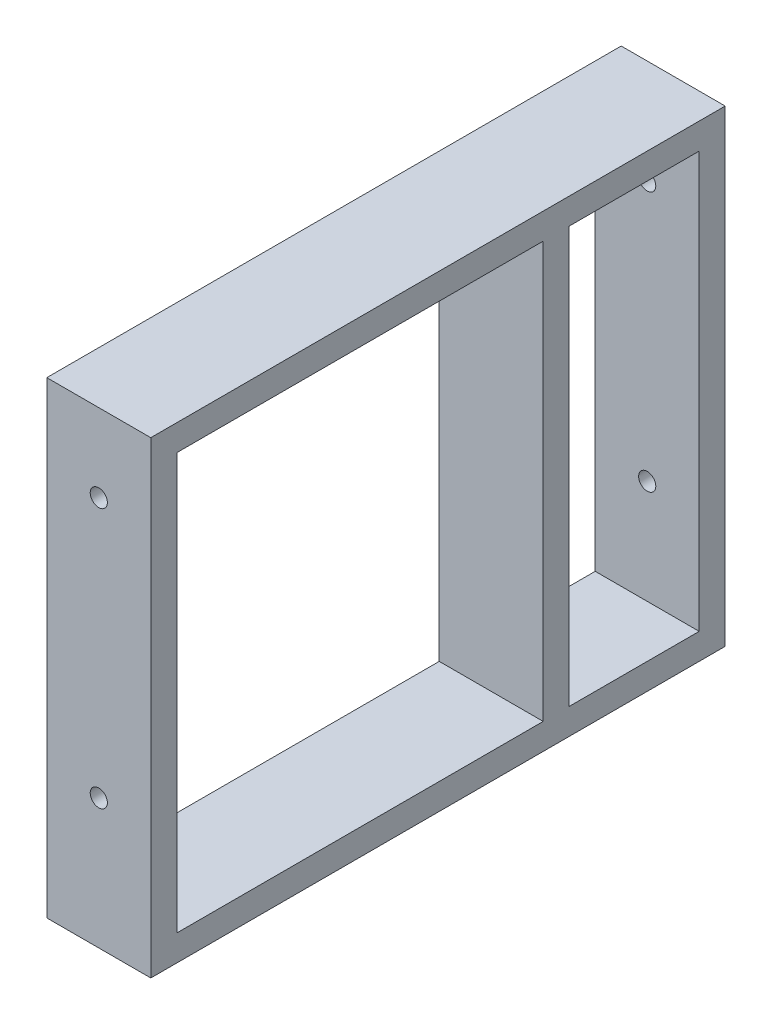
SolidWorks part; units mm, degrees
ref_plane "Front Plane" through (0, 0, 0) normal (0, 0, 1) x (1, 0, 0)
ref_plane "Top Plane" through (0, 0, 0) normal (0, 1, 0) x (1, 0, 0)
ref_plane "Right Plane" through (0, 0, 0) normal (1, 0, 0) x (0, 0, -1)
sketch "Sketch1" plane through (0, 0, 0) normal (1, 0, 0) x (0, 0, -1)
  line L1 (-55.2375, -45) -> (55.2375, -45)
  line L2 (-55.2375, -45) -> (-55.2375, 45)
  line L3 (-55.2375, 45) -> (55.2375, 45)
  line L4 (55.2375, -45) -> (55.2375, 45)
  line L5 (-55.2375, -45) -> (55.2375, 45) construction
  line L6 (-55.2375, 45) -> (55.2375, -45) construction
  line L7 (-50.2375, -40) -> (50.2375, -40)
  line L8 (-50.2375, -40) -> (-50.2375, 40)
  line L9 (-50.2375, 40) -> (50.2375, 40)
  line L10 (50.2375, -40) -> (50.2375, 40)
  line L11 (-50.2375, -40) -> (50.2375, 40) construction
  line L12 (-50.2375, 40) -> (50.2375, -40) construction
  line L13 (20.2375, -40) -> (25.2375, -40)
  line L14 (20.2375, -40) -> (20.2375, 40)
  line L15 (20.2375, 40) -> (25.2375, 40)
  line L16 (25.2375, -40) -> (25.2375, 40)
  line L17 (20.2375, -40) -> (25.2375, 40) construction
  line L18 (20.2375, 40) -> (25.2375, -40) construction
  point P0 (0, 0)
  point P6 (0, 0)
  point P11 (22.7375, 0)
  point P16 (0, 0)
  dimension "D1" = 110.475
  dimension "D2" = 90
  dimension "D3" = 5
  dimension "D4" = 5
  dimension "D5" = 5
  dimension "D6" = 25
extrude "Boss-Extrude1" add sketch "Sketch1" along normal blind 20 contours L1 L4 L3 L2 L10 L7 L8 L9 | L7 L16 L9 L14 region at (0, 0, 53.8126) region at (0, 0, -22.7375)
hole_wizard "M4 Clearance Hole1" positions "Sketch2" profile "Sketch3" hole size "M4" standard "ANSI Metric"
sketch "Sketch2" plane through (0, -40, 0) normal (0, 1, 0) x (1, 0, 0)
  line L0 (10, 30.2375) -> (10, -44.7625)
  line L2 (0, -55.2375) -> (0, 55.2375) construction
  point P1 (10, 30.2375)
  point P2 (10, -44.7625)
  dimension "D1" = 75
  dimension "D2" = 10
  dimension "D3" = 25
sketch "Sketch3" plane through (10, -40, -30.2375) normal (1, 0, 0) x (0, 0, 1)
  line L0 (0, 0) -> (0, 9.1519)
  line L1 (0, 9.1519) -> (2.25, 7.8)
  line L2 (2.25, 7.8) -> (2.25, 0)
  line L5 (2.25, 0) -> (0, 0)
  line L10 (0, 9.1519) -> (-2.25, 7.8) construction
  line L11 (0, -6.35) -> (0, 107.95) construction
  dimension "Hole Dia." = 4.5
  dimension "Hole Depth" = 7.8
  dimension "Drill Angle" = 118
hole_wizard "M4x0.7 Tapped Hole1" positions "Sketch4" profile "Sketch6" tap size "M4x0.7" standard "ANSI Metric"
sketch "Sketch4" plane through (0, 0, 55.2375) normal (0, 0, 1) x (1, 0, 0)
  line L0 (10, 30) -> (10, -20)
  line L2 (0, -45) -> (0, 45) construction
  line L3 (20, -45) -> (0, -45) construction
  point P0 (10, 30)
  point P1 (10, -20)
  dimension "D1" = 50
  dimension "D2" = 10
  dimension "D3" = 25
sketch "Sketch6" plane through (10, 30, 55.2375) normal (1, 0, 0) x (0, -1, 0)
  line L0 (0, 0) -> (0, 11.0914)
  line L1 (0, 11.0914) -> (1.65, 10.1)
  line L2 (1.65, 10.1) -> (1.65, 0)
  line L5 (1.65, 0) -> (0, 0)
  line L10 (0, 11.0914) -> (-1.65, 10.1) construction
  line L11 (0, -6.35) -> (0, 107.95) construction
  dimension "Tap Drill Dia." = 3.3
  dimension "Tap Drill Depth" = 10.1
  dimension "Drill Angle" = 118
cosmetic thread "Hole Thread1" parameters "D1"=8, "D2"=4
cosmetic thread "Hole Thread2" parameters "D1"=8, "D2"=4
mirror "Mirror1" about plane through (0, 0, 0) normal (0, 0, 1) of "M4x0.7 Tapped Hole1"
cosmetic thread "Hole Thread3" parameters "D1"=8, "D2"=4
cosmetic thread "Hole Thread4" parameters "D1"=8, "D2"=4
